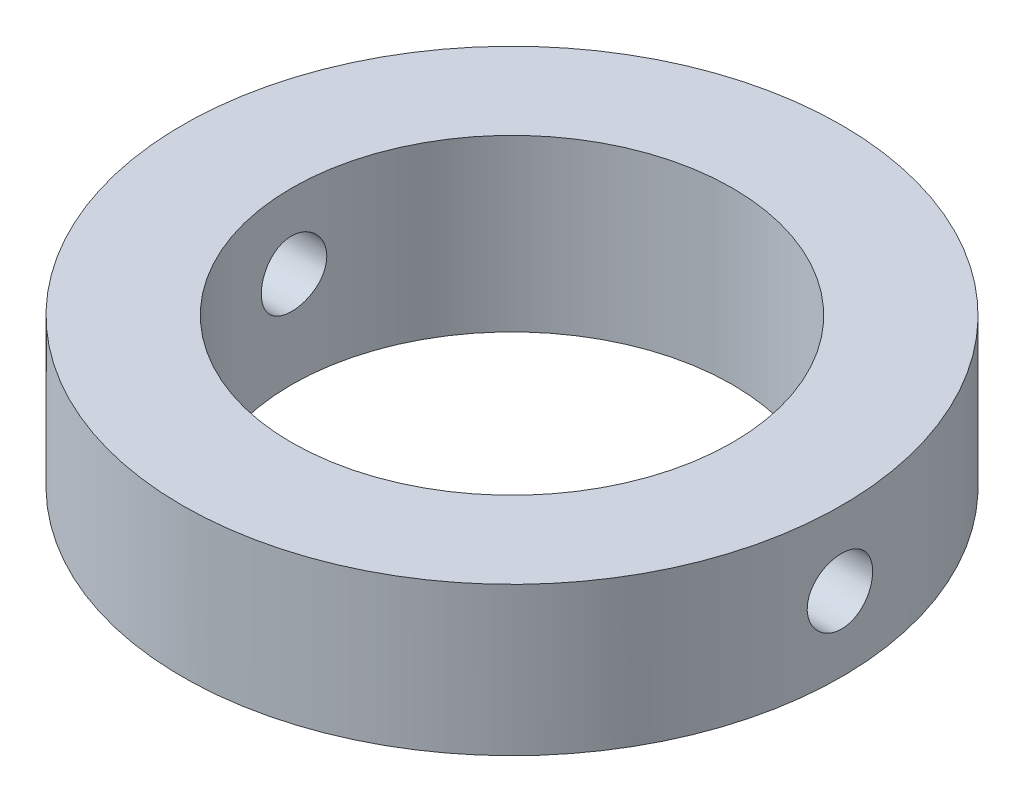
SolidWorks part; units mm, degrees
ref_plane "Front Plane" through (0, 0, 0) normal (0, 0, 1) x (1, 0, 0)
ref_plane "Top Plane" through (0, 0, 0) normal (0, 1, 0) x (1, 0, 0)
ref_plane "Right Plane" through (0, 0, 0) normal (1, 0, 0) x (0, 0, -1)
sketch "Sketch1" plane through (0, 0, 0) normal (0, 1, 0) x (1, 0, 0)
  circle A0 centre (0, 0) radius 10.1
  circle A1 centre (0, 0) radius 15.1
extrude "Boss-Extrude1" add sketch "Sketch1" along normal blind 7
sketch "Sketch2" plane through (0, 0, 0) normal (1, 0, 0) x (0, 0, -1)
  line L0 (0, 7) -> (0, 0)
  line L1 (10.1, 7) -> (-10.1, 7) construction
  line L2 (0, 0) -> (0, 3.5)
  line L3 (0, 3.5) -> (0, 4.402)
  circle A1 centre (0, 4.402) radius 1.5
extrude "Cut-Extrude3" cut sketch "Sketch2" along normal blind 22 and the other way blind 24 contours L0 A1 | L0 A1 region at (0, 4.402, -0.6366) region at (0, 4.402, 0.6366)
sketch "Sketch4" plane through (0, 0, 0) normal (0, -1, 0) x (1, 0, 0)
  circle A0 centre (0, 0) radius 11.1
  circle A1 centre (0, 0) radius 23.3538
extrude "Cut-Extrude4" cut sketch "Sketch4" against normal blind 1
sketch "Sketch6" plane through (0, 7, 0) normal (0, 1, 0) x (1, 0, 0)
  circle A0 centre (0, 0) radius 10.1 construction
  circle A1 centre (0, 0) radius 15.1 construction
  circle A2 centre (0, 0) radius 10.1
  circle A3 centre (0, 0) radius 15.1
extrude "Boss-Extrude2" add sketch "Sketch6" along normal blind 0.8
